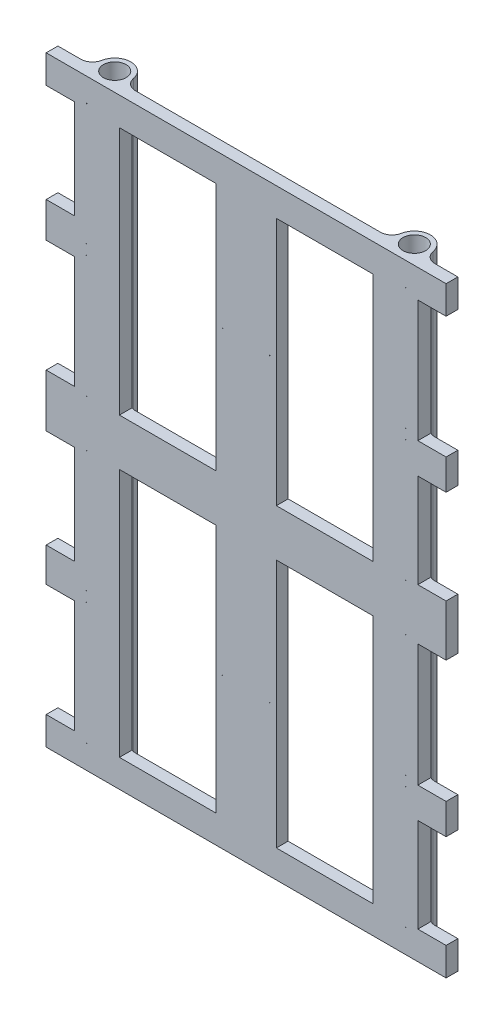
SolidWorks part; units mm, degrees
material "E-Glass Fiber"
ref_plane "Front Plane" through (0, 0, 0) normal (0, 0, 1) x (1, 0, 0)
ref_plane "Top Plane" through (0, 0, 0) normal (0, 1, 0) x (1, 0, 0)
ref_plane "Right Plane" through (0, 0, 0) normal (1, 0, 0) x (0, 0, -1)
other "Center of Mass"
sketch "Sketch1" plane through (0, 0, 0) normal (0, 1, 0) x (1, 0, 0)
  line L19 (85, -5) -> (85, 0)
  line L20 (85, -5) -> (-85, -5)
  line L24 (85, 0) -> (75.3042, 0)
  line L25 (-85, -5) -> (-85, 0)
  line L26 (85, -5) -> (-85, 0) construction
  line L27 (85, 0) -> (-85, -5) construction
  line L28 (0, 0) -> (0, -5) construction
  line L29 (-75.3042, 0) -> (-85, 0)
  line L30 (52.0558, 0) -> (-52.0558, 0)
  circle A29 centre (-63.68, 2.83) radius 4.825
  arc A30 (-69.8906, 0) -> (-57.4694, 0) centre (-63.68, 2.83) ccw construction
  arc A31 (-75.3042, 0) -> (-70.3891, 4.0825) centre (-75.3042, 5) ccw
  arc A32 (-56.9709, 4.0825) -> (-52.0558, 0) centre (-52.0558, 5) ccw
  arc A33 (-56.9709, 4.0825) -> (-70.3891, 4.0825) centre (-63.68, 2.83) ccw
  arc A34 (69.8906, 0) -> (57.4694, 0) centre (63.68, 2.83) cw construction
  arc A35 (56.9709, 4.0825) -> (70.3891, 4.0825) centre (63.68, 2.83) cw
  arc A36 (56.9709, 4.0825) -> (52.0558, 0) centre (52.0558, 5) cw
  arc A37 (75.3042, 0) -> (70.3891, 4.0825) centre (75.3042, 5) cw
  circle A38 centre (63.68, 2.83) radius 4.825
  point P1 (0, -2.5)
  dimension "D3" = 9.65
  dimension "D4" = 7.83
  dimension "D5" = 63.68
  dimension "D6" = 13.65
  dimension "D1" = 5
  dimension "D2" = 170
extrude "Boss-Extrude1" add sketch "Sketch1" along normal blind 255.6
sketch "Sketch2" plane through (0, 0, 0) normal (0, 0, -1) x (-1, 0, 0)
  line L0 (-85, 127.8) -> (85, 127.8) construction
  line L1 (-53.855, 11.8) -> (-12.855, 11.8)
  line L2 (-53.855, 11.8) -> (-53.855, 117.8)
  line L3 (-53.855, 243.6) -> (-12.855, 243.6)
  line L4 (-12.855, 11.8) -> (-12.855, 117.8)
  line L5 (-53.855, 11.8) -> (-12.855, 243.6) construction
  line L6 (-53.855, 243.6) -> (-12.855, 11.8) construction
  line L7 (-52.0558, 255.6) -> (52.0558, 255.6) construction
  line L8 (-12.855, 137.8) -> (-12.855, 243.6)
  line L9 (0, 255.6) -> (0, 0) construction
  line L10 (-93, 178.8) -> (-73, 178.8)
  line L11 (53.855, 11.8) -> (12.855, 11.8)
  line L12 (53.855, 11.8) -> (53.855, 117.8)
  line L13 (53.855, 243.6) -> (12.855, 243.6)
  line L14 (12.855, 11.8) -> (12.855, 117.8)
  line L15 (53.855, 11.8) -> (12.855, 243.6) construction
  line L16 (53.855, 243.6) -> (12.855, 11.8) construction
  line L17 (-58.855, 0) -> (-58.855, 255.6) construction
  line L18 (58.855, 255.6) -> (58.855, 0) construction
  line L19 (12.855, 137.8) -> (12.855, 243.6)
  line L20 (-53.855, 117.8) -> (-12.855, 117.8)
  line L22 (-53.855, 137.8) -> (-12.855, 137.8)
  line L24 (12.855, 137.8) -> (53.855, 137.8)
  line L25 (12.855, 117.8) -> (53.855, 117.8)
  line L26 (-53.855, 137.8) -> (-53.855, 243.6)
  line L27 (53.855, 137.8) -> (53.855, 243.6)
  line L28 (-93, 178.8) -> (-93, 138.8)
  line L29 (-93, 138.8) -> (-73, 138.8)
  line L30 (-73, 178.8) -> (-73, 138.8)
  line L31 (-93, 178.8) -> (-73, 138.8) construction
  line L32 (-93, 138.8) -> (-73, 178.8) construction
  line L33 (-85, 255.6) -> (-85, 0) construction
  line L34 (85, 255.6) -> (85, 0) construction
  line L35 (-93, 52) -> (-73, 52)
  line L36 (-73, 191.8) -> (-93, 191.8)
  line L37 (-73, 191.8) -> (-73, 243.6)
  line L38 (-73, 243.6) -> (-93, 243.6)
  line L39 (-93, 191.8) -> (-93, 243.6)
  line L40 (-73, 191.8) -> (-93, 243.6) construction
  line L41 (-73, 243.6) -> (-93, 191.8) construction
  line L42 (-93, 52) -> (-93, 12)
  line L43 (-93, 12) -> (-73, 12)
  line L44 (-73, 52) -> (-73, 12)
  line L53 (-93, 52) -> (-73, 12) construction
  line L54 (-93, 12) -> (-73, 52) construction
  line L55 (-73, 65) -> (-93, 65)
  line L56 (-73, 65) -> (-73, 117)
  line L57 (-73, 117) -> (-93, 117)
  line L58 (-93, 65) -> (-93, 117)
  line L59 (-73, 65) -> (-93, 117) construction
  line L60 (-73, 117) -> (-93, 65) construction
  line L61 (75.3042, 255.6) -> (85, 255.6) construction
  line L62 (-85, 0) -> (-75.3042, 0) construction
  line L67 (93, 201.6) -> (73, 201.6)
  line L68 (93, 201.6) -> (93, 243.6)
  line L73 (93, 243.6) -> (73, 243.6)
  line L74 (73, 201.6) -> (73, 243.6)
  line L75 (-85, 255.6) -> (-75.3042, 255.6) construction
  line L76 (93, 74.4) -> (73, 74.4)
  line L77 (93, 201.6) -> (73, 243.6) construction
  line L78 (93, 243.6) -> (73, 201.6) construction
  line L83 (73, 138.8) -> (93, 138.8)
  line L84 (73, 138.8) -> (73, 186.6)
  line L85 (73, 186.6) -> (93, 186.6)
  line L86 (93, 138.8) -> (93, 186.6)
  line L87 (73, 138.8) -> (93, 186.6) construction
  line L88 (73, 186.6) -> (93, 138.8) construction
  line L89 (93, 74.4) -> (93, 116.4)
  line L90 (93, 116.4) -> (73, 116.4)
  line L91 (73, 74.4) -> (73, 116.4)
  line L92 (93, 74.4) -> (73, 116.4) construction
  line L93 (93, 116.4) -> (73, 74.4) construction
  line L94 (73, 12) -> (93, 12)
  line L95 (73, 12) -> (73, 59.9)
  line L96 (73, 59.9) -> (93, 59.9)
  line L97 (93, 12) -> (93, 59.9)
  line L98 (73, 12) -> (93, 59.9) construction
  line L99 (73, 59.9) -> (93, 12) construction
  line L100 (75.3042, 0) -> (85, 0) construction
  point P0 (-33.355, 127.7)
  point P5 (-83, 158.8)
  point P14 (33.355, 127.7)
  point P23 (0, 127.8)
  point P39 (-83, 217.7)
  point P44 (-83, 32)
  point P49 (-83, 91)
  point P54 (83, 222.6)
  point P61 (83, 162.7)
  point P70 (83, 95.4)
  point P75 (83, 35.95)
  dimension "D1" = 12
  dimension "D2" = 5
  dimension "D3" = 41
  dimension "D4" = 12
  dimension "D5" = 5
  dimension "D6" = 41
  dimension "D7" = 20
  dimension "D8" = 11
  dimension "D9" = 40
  dimension "D10" = 73
  dimension "D11" = 20
  dimension "D12" = 13
  dimension "D13" = 12
  dimension "D14" = 40
  dimension "D15" = 20
  dimension "D16" = 13
  dimension "D17" = 52
  dimension "D18" = 73
  dimension "D19" = 20
  dimension "D20" = 12
  dimension "D21" = 12
  dimension "D22" = 15
  dimension "D23" = 42
  dimension "D24" = 73
  dimension "D25" = 11
  dimension "D26" = 20
  dimension "D27" = 14.5
  dimension "D28" = 42
  dimension "D29" = 73
  dimension "D30" = 12
extrude "Cut-Extrude2" cut sketch "Sketch2" against normal through all and the other way through all
sketch "Sketch5" plane through (0, 0, 5) normal (0, 0, 1) x (1, 0, 0)
  line L1 (0, 255.8) -> (0, 0) construction
  line L6 (-85, 255.6) -> (85, 255.6) construction
  line L7 (0, 191.7) -> (131.7924, 191.7) construction
  line L13 (68.505, 127.8) -> (-68.505, 127.8) construction
  line L14 (68.505, 0) -> (68.505, 255.6) construction
  line L15 (-68.505, 255.6) -> (-68.505, 0) construction
  point P7 (67.775, 245.575)
  point P26 (67.9, 193.825)
  point P33 (10.025, 191.7)
  point P48 (67.9, 189.575)
  point P49 (67.775, 137.825)
  point P50 (-67.775, 137.825)
  point P51 (-67.9, 189.575)
  point P52 (-67.9, 193.825)
  point P53 (-67.775, 245.575)
  point P54 (-10.025, 191.7)
  point P85 (-10.025, 63.9)
  point P86 (-67.775, 10.025)
  point P87 (-67.9, 61.775)
  point P88 (-67.9, 66.025)
  point P89 (-67.775, 117.775)
  point P90 (67.775, 117.775)
  point P91 (67.9, 66.025)
  point P92 (10.025, 63.9)
  point P93 (67.9, 61.775)
  point P94 (67.775, 10.025)
  dimension "D1" = 67.775
  dimension "D2" = 10.025
  dimension "D3" = 61.775
  dimension "D4" = 63.9
  dimension "D5" = 10.025
hole_wizard "Ø0.25 (0.25) Diameter Hole1" positions "Sketch5" profile "Sketch4" hole size "Ø0.25" standard "ANSI Metric"
sketch "Sketch4" plane through (67.775, 10.025, 5) normal (1, 0, 0) x (0, -1, 0)
  line L0 (0, 0) -> (0, 2)
  line L1 (0, 2) -> (0.125, 1.9249)
  line L2 (0.125, 1.9249) -> (0.125, 0)
  line L5 (0.125, 0) -> (0, 0)
  line L10 (0, 2) -> (-0.125, 1.9249) construction
  line L11 (0, -6.35) -> (0, 107.95) construction
  dimension "Hole Dia." = 0.25
  dimension "Hole Depth" = 2
  dimension "Drill Angle" = 118
equation "\"rod_d\"= 9.65"
equation "\"big_bearing_id\"= 140mm"
equation "\"rod_offset_c2c\"= \"big_bearing_id\" / 2 - \"rod_d\" / 2 - 1.5"
